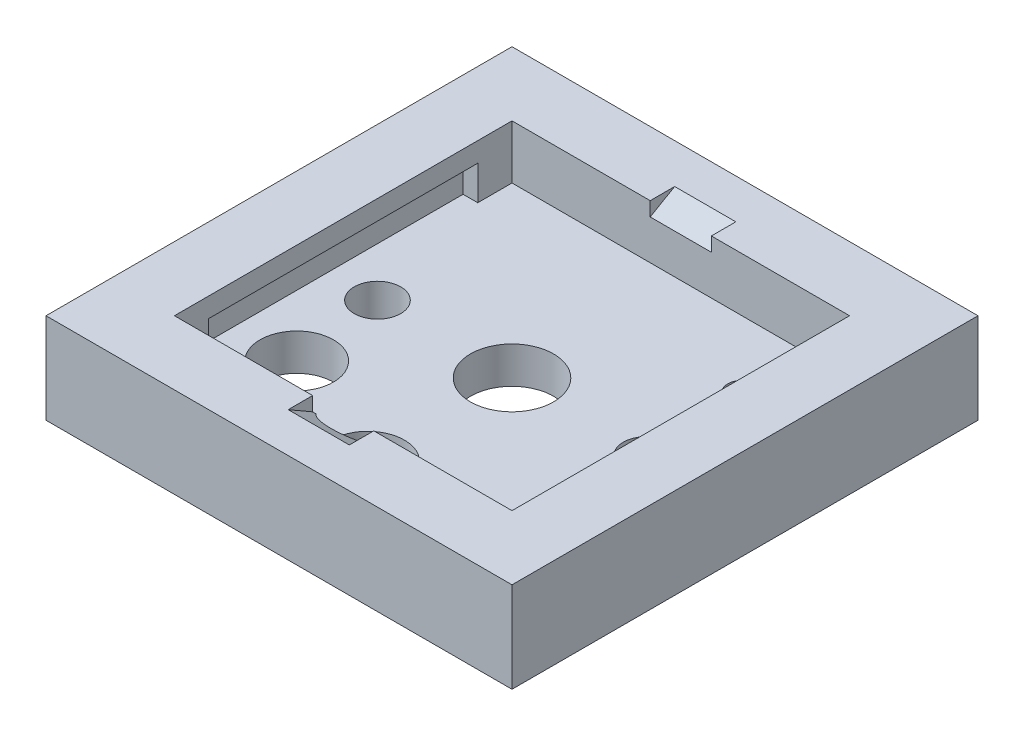
SolidWorks part; units mm, degrees
other "single-1350"
ref_plane "Front Plane" through (0, 0, 0) normal (0, 0, 1) x (1, 0, 0)
ref_plane "Top Plane" through (0, 0, 0) normal (0, 1, 0) x (1, 0, 0)
ref_plane "Right Plane" through (0, 0, 0) normal (1, 0, 0) x (0, 0, -1)
sketch "Sketch1" plane through (0, 0, 0) normal (0, 1, 0) x (1, 0, 0)
  line L0 (-6.9, 6.9) -> (6.9, 6.9)
  line L1 (6.9, 6.9) -> (6.9, -6.9)
  line L2 (6.9, -6.9) -> (1.118, -6.9)
  line L3 (-6.9, -6.9) -> (-6.9, 6.9)
  line L4 (13.0003, 0) -> (-13.0003, 0) construction
  line L5 (0, 13.0493) -> (0, -13.0493) construction
  line L6 (-1.118, -6.9) -> (-6.9, -6.9)
  line L8 (-9.525, -9.525) -> (9.525, -9.525)
  line L9 (-9.525, -9.525) -> (-9.525, 9.525)
  line L10 (-9.525, 9.525) -> (9.525, 9.525)
  line L11 (9.525, -9.525) -> (9.525, 9.525)
  line L12 (-9.525, -9.525) -> (9.525, 9.525) construction
  line L13 (-9.525, 9.525) -> (9.525, -9.525) construction
  circle A0 centre (0, 0) radius 1.7
  circle A1 centre (-5.5, 0) radius 0.95
  circle A2 centre (5.5, 0) radius 0.95
  circle A3 centre (-5, -3.8) radius 1.5
  circle A4 centre (0, -5.9) radius 1.5
  circle A5 centre (5.22, 4.2) radius 0.6
  point P20 (0, 0)
  point P23 (0, 0)
  dimension "D1" = 11
  dimension "D2" = 1.9
  dimension "D3" = 3
  dimension "D5" = 3.4
  dimension "D8" = 1.2
  dimension "D13" = 6.9
  dimension "D16" = 19.05
  dimension "D4" = 5
  dimension "D6" = 5.9
  dimension "D7" = 4.2
  dimension "D9" = 13.8
  dimension "D10" = 5.22
  dimension "D11" = 3.8
  dimension "D12" = 6.9
  dimension "D14" = 5.5
  dimension "D15" = 19.05
extrude "Boss-Extrude1" add sketch "Sketch1" along normal blind 3.7 contours L8 L11 L10 L9 A4 L6 L3 L0 L1 L2 | A4 L2 L1 L0 L3 L6 A5 A0 A1 A2 A3 region at (0, 0, -6.7048) region at (-9.2556, 0, 0)
extrude "Cut-Extrude1" cut sketch "Sketch1<3>" against normal blind 2.2 from surface contours A4 L2 L1 L0 L3 L6 A5 A0 A1 A2 A3 region at (0, 0, -6.7048) starting at face at (0, 3.7, 7.4)
sketch "Sketch1<3>" plane through (0, 0, 0) normal (0, 1, 0) x (1, 0, 0) same geometry as "Sketch1"
sketch "Sketch2" plane through (0, 0, 0) normal (1, 0, 0) x (0, 0, -1)
  line L0 (-7.9, 3.7) -> (-6.9, 3.7)
  line L1 (-6.9, 3.7) -> (-6.9, 3.1226)
  line L2 (-6.9, 3.1226) -> (-7.9, 3.7)
  line L3 (-6.9, 1.5) -> (-6.9, 3.7) construction
  dimension "D1" = 150
  dimension "D2" = 1
extrude "Cut-Extrude2" cut sketch "Sketch2" against normal mid plane 2.5
mirror "Mirror1" about plane through (0, 0, 0) normal (0, 0, 1) of "Cut-Extrude2"
sketch "Sketch4" plane through (0, 0, 0) normal (0, 0, 1) x (1, 0, 0)
  line L2 (-6.9, 2.9) -> (-6.9, 1.5)
  line L3 (-6.9, 1.5) -> (-7.5, 1.5)
  line L4 (-7.5, 2.8) -> (-7.5, 1.5)
  line L5 (-6.9, 3.7) -> (-7.5, 1.5) construction
  line L10 (-7.5, 2.8) -> (-7, 2.8)
  line L11 (-7, 2.8) -> (-6.9, 2.9)
  line L12 (-6.9, 3.7) -> (-6.9, 2.9) construction
  dimension "D1" = 0.9
  dimension "D2" = 0.6
  dimension "D4" = 45
  dimension "D5" = 0.5
extrude "Cut-Extrude3" cut sketch "Sketch4" against normal mid plane 11
mirror "Mirror2" about plane through (0, 0, 0) normal (1, 0, 0) of "Cut-Extrude3"
equation "\"key_spacing\"= 19.05mm"
